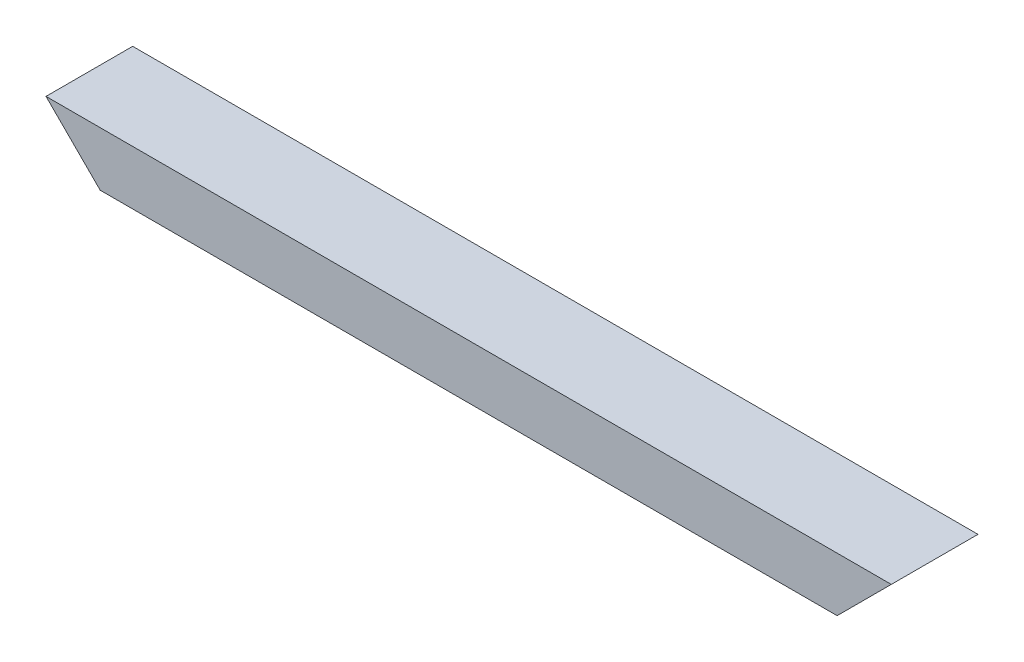
SolidWorks part; units mm, degrees
material "1023 Carbon Steel Sheet (SS)"
ref_plane "Front Plane" through (0, 0, 0) normal (0, 0, 1) x (1, 0, 0)
ref_plane "Top Plane" through (0, 0, 0) normal (0, 1, 0) x (1, 0, 0)
ref_plane "Right Plane" through (0, 0, 0) normal (1, 0, 0) x (0, 0, -1)
sketch "Sketch2" plane through (0, 0, 0) normal (0, 0, 1) x (1, 0, 0)
  line L0 (0, 0) -> (863.6, 0)
  line L1 (863.6, 0) -> (927.1, 63.5)
  line L2 (927.1, 63.5) -> (-63.5, 63.5)
  line L3 (-63.5, 63.5) -> (0, 0)
  dimension "D1" = 135
  dimension "D2" = 135
  dimension "D3" = 863.6
  dimension "D4" = 63.5
extrude "Boss-Extrude1" add sketch "Sketch2" along normal blind 101.6
